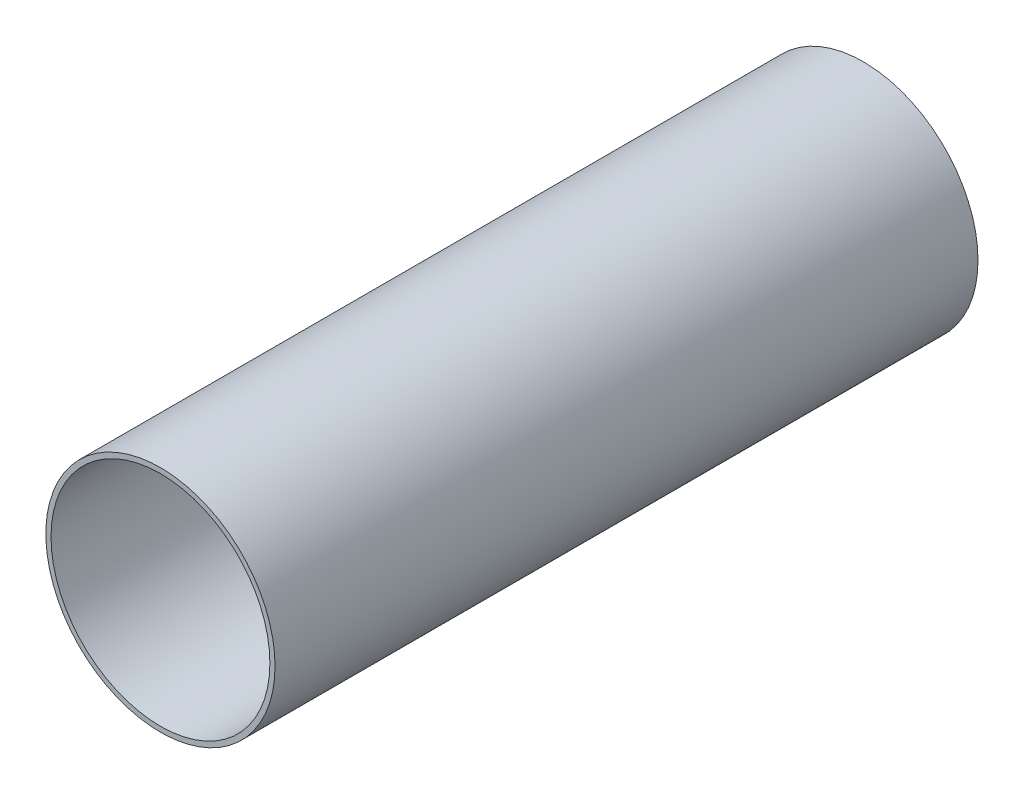
SolidWorks part; units mm, degrees
ref_plane "Front Plane" through (0, 0, 0) normal (0, 0, 1) x (1, 0, 0)
ref_plane "Top Plane" through (0, 0, 0) normal (0, 1, 0) x (1, 0, 0)
ref_plane "Right Plane" through (0, 0, 0) normal (1, 0, 0) x (0, 0, -1)
ref_axis "Axis1" through (0, 0, -88.99) along (0, 0, 1)
sketch "Sketch1" plane through (0, 0, 0) normal (0, 0, 1) x (1, 0, 0)
  circle A0 centre (0, 0) radius 26.543
  circle A1 centre (0, 0) radius 25.3492
  dimension "D1" = 50.6984
  dimension "D2" = 53.086
extrude "Boss-Extrude1" add sketch "Sketch1" along normal mid plane 162.814
